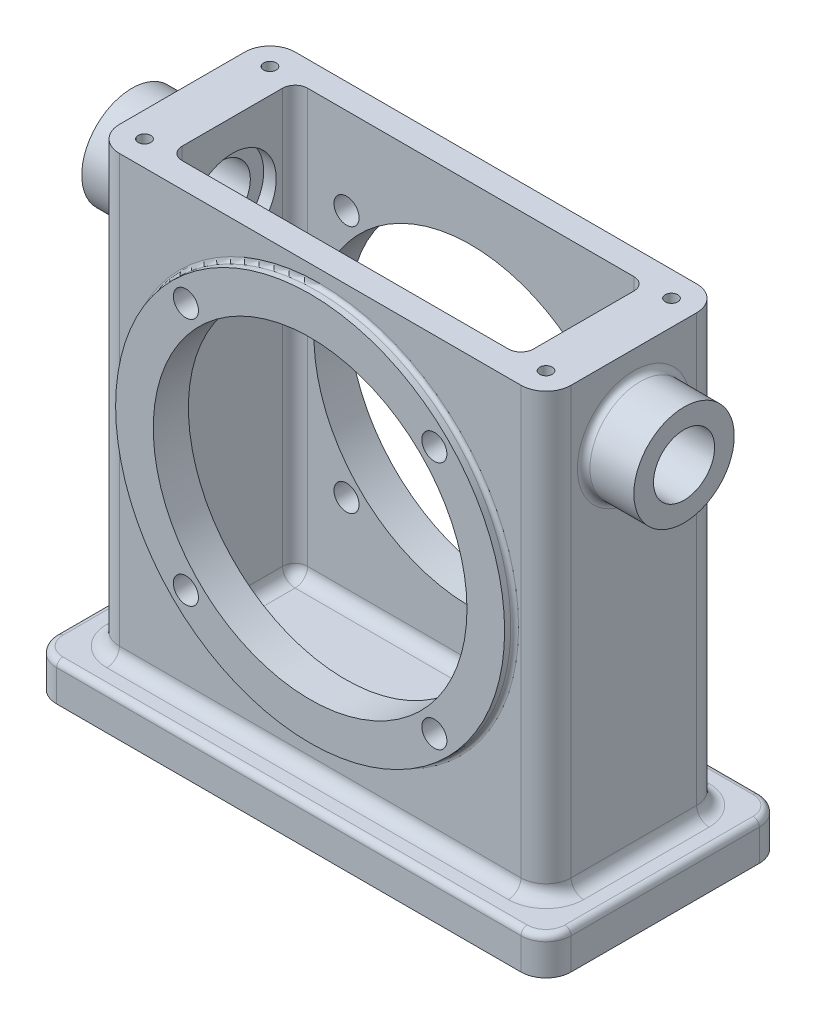
SolidWorks part; units mm, degrees
note: '?' marks a value the reader was unsure of.
ref_plane "Front" through (0, 0, 0) normal (0, 0, 1) x (1, 0, 0)
ref_plane "Top" through (0, 0, 0) normal (0, 1, 0) x (1, 0, 0)
ref_plane "Right" through (0, 0, 0) normal (1, 0, 0) x (0, 0, -1)
other "Configuration Table"
sketch "Sketch1" plane through (0, 0, 0) normal (0, 1, 0) x (1, 0, 0)
  line L0 (-65.0875, -30.1625) -> (65.0875, 30.1625) construction
  line L1 (-65.0875, -30.1625) -> (65.0875, -30.1625)
  line L2 (-65.0875, -30.1625) -> (-65.0875, 30.1625)
  line L3 (-65.0875, 30.1625) -> (65.0875, 30.1625)
  line L4 (65.0875, -30.1625) -> (65.0875, 30.1625)
  dimension "D1" = 130.175
  dimension "D2" = 60.325
extrude "Base-Extrude" add sketch "Sketch1" along normal blind 9.525
sketch "Sketch2" plane through (0, 9.525, 0) normal (0, 1, 0) x (-1, 0, 0)
  line L0 (57.15, 22.225) -> (-57.15, -22.225) construction
  line L1 (57.15, 22.225) -> (-57.15, 22.225)
  line L2 (57.15, 22.225) -> (57.15, -22.225)
  line L3 (57.15, -22.225) -> (-57.15, -22.225)
  line L4 (-57.15, 22.225) -> (-57.15, -22.225)
  dimension "D1" = 114.3
  dimension "D2" = 44.45
extrude "Boss-Extrude1" add sketch "Sketch2" along normal blind 111.125
fillet "Fillet1" radius 6.35 8 edges at (-57.15, 65.0875, -22.225) (-57.15, 65.0875, 22.225) (57.15, 65.0875, 22.225) (57.15, 65.0875, -22.225) (-65.0875, 4.7625, -30.1625) (65.0875, 4.7625, -30.1625) (65.0875, 4.7625, 30.1625) (-65.0875, 4.7625, 30.1625)
fillet "Fillet2" radius 1.5875 8 edges at (0, 9.525, 30.1625) (-65.0875, 9.525, 0) (65.0875, 9.525, 0) (0, 9.525, -30.1625) (-63.2276, 9.525, -28.3026) (63.2276, 9.525, 28.3026) (63.2276, 9.525, -28.3026) (-63.2276, 9.525, 28.3026)
fillet "Fillet3" radius 3.175 8 edges at (-57.15, 9.525, 0) (0, 9.525, -22.225) (57.15, 9.525, 0) (0, 9.525, 22.225) (-55.2901, 9.525, 20.3651) (-55.2901, 9.525, -20.3651) (55.2901, 9.525, 20.3651) (55.2901, 9.525, -20.3651)
sketch "Sketch3" plane through (0, 120.65, 0) normal (0, 1, 0) x (-1, 0, 0)
  line L2 (50.8, 15.875) -> (-50.8, 15.875)
  line L3 (41.275, 15.875) -> (-41.275, 15.875)
  line L5 (-50.8, -15.875) -> (50.8, -15.875)
  line L6 (-41.275, -15.875) -> (41.275, -15.875)
  line L8 (44.45, -15.875) -> (44.45, 15.875)
  line L9 (44.45, -12.7) -> (44.45, 12.7)
  line L11 (-44.45, 15.875) -> (-44.45, -15.875)
  line L12 (-44.45, 12.7) -> (-44.45, -12.7)
  arc A0 (-41.275, 15.875) -> (-44.45, 12.7) centre (-41.275, 12.7) ccw
  arc A1 (44.45, 12.7) -> (41.275, 15.875) centre (41.275, 12.7) ccw
  arc A2 (41.275, -15.875) -> (44.45, -12.7) centre (41.275, -12.7) ccw
  arc A3 (-44.45, -12.7) -> (-41.275, -15.875) centre (-41.275, -12.7) ccw
  dimension "D5" = 3.175
  dimension "D1" = 6.35
  dimension "D2" = 6.35
  dimension "D3" = 12.7
  dimension "D4" = 12.7
extrude "Cut-Extrude1" cut sketch "Sketch3" against normal blind 107.95
fillet "Fillet4" radius 3.175 8 edges at (43.5201, 12.7, 14.9451) (0, 12.7, 15.875) (-43.5201, 12.7, 14.9451) (-44.45, 12.7, 0) (-43.5201, 12.7, -14.9451) (0, 12.7, -15.875) (43.5201, 12.7, -14.9451) (44.45, 12.7, 0)
sketch "Sketch4" plane through (0, 0, 22.225) normal (0, 0, 1) x (1, 0, 0)
  line L0 (-50.8, 120.65) -> (50.8, 120.65) construction
  line L1 (0, -50) -> (0, 50) construction
  circle A0 centre (0, 67.31) radius 49.2125
  dimension "D1" = 98.425
  dimension "D2" = 53.34
extrude "Boss-Extrude2" add sketch "Sketch4" along normal blind 2.54
mirror "Mirror1" about plane through (0, 0, 0) normal (0, 0, 1) of "Boss-Extrude2"
sketch "Sketch5" plane through (0, 0, 24.765) normal (0, 0, 1) x (1, 0, 0)
  circle A0 centre (0, 67.31) radius 39.6875
  dimension "D1" = 79.375
extrude "Cut-Extrude2" cut sketch "Sketch5" against normal through all
fillet "Fillet5" radius 0.9906 2 edges at (-49.2125, 67.31, 22.225) (49.2125, 67.31, -22.225)
sketch "Sketch6" plane through (57.15, 0, 0) normal (1, 0, 0) x (0, 0, -1)
  line L0 (-23.8125, 0) -> (23.8125, 0) construction
  line L1 (0, 101.6) -> (0, 0) construction
  circle A0 centre (0, 101.6) radius 12.7
  dimension "D1" = 25.4
  dimension "D2" = 101.6
extrude "Boss-Extrude3" add sketch "Sketch6" along normal blind 12.7
sketch "Sketch7" plane through (44.45, 0, 0) normal (-1, 0, 0) x (0, 0, 1)
  circle A0 centre (0, 101.6) radius 7.7343
  dimension "D1" = 15.4686
extrude "Cut-Extrude3" cut sketch "Sketch7" against normal through all
sketch "Sketch8" plane through (44.45, 0, 0) normal (-1, 0, 0) x (0, 0, 1)
  circle A0 centre (0, 101.6) radius 11.1125
  dimension "D1" = 22.225
extrude "Cut-Extrude4" cut sketch "Sketch8" against normal blind 3.175
mirror "Mirror3" about plane through (0, 0, 0) normal (1, 0, 0) of "Cut-Extrude4", "Cut-Extrude3", "Boss-Extrude3"
fillet "Fillet6" radius 1.5875 2 edges at (57.15, 101.6, 12.7) (-57.15, 101.6, -12.7)
sketch "Sketch9" plane through (0, 0, 24.765) normal (0, 0, 1) x (1, 0, 0)
  line L0 (31.4309, 98.7409) -> (0, 67.31) construction
  line L1 (0, 67.31) -> (44.45, 67.31) construction
  circle A0 centre (0, 67.31) radius 44.45 construction
  circle A1 centre (31.4309, 98.7409) radius 3.175
  dimension "D1" = 88.9
  dimension "D2" = 6.35
  dimension "D3" = 45
extrude "Cut-Extrude5" cut sketch "Sketch9" against normal through all
ref_axis "CenterLargeHole" through (0, 67.31, -83.0711) along (0, 0, 1)?
pattern_circular "CirPattern1" count 4 over 360 about axis through (0, 67.31, 0) along (0, 0, 1) of "Cut-Extrude5"
sketch "Sketch10" plane through (0, 120.65, 0) normal (0, 1, 0) x (-1, 0, 0)
  line L0 (-41.275, -15.875) -> (41.275, -15.875) construction
  line L1 (41.275, 15.875) -> (-41.275, 15.875) construction
  line L2 (-57.15, 15.875) -> (-57.15, -15.875) construction
  circle A0 centre (-50.8, -15.875) radius 1.5875
  circle A1 centre (-50.8, 15.875) radius 1.5875
  dimension "D1" = 3.175
  dimension "D2" = 6.35
extrude "Cut-Extrude6" cut sketch "Sketch10" against normal blind 19.05
mirror "Mirror4" about plane through (0, 0, 0) normal (1, 0, 0) of "Cut-Extrude6"
sketch "Sketch11" plane through (0, 120.65, 0) normal (0, 1, 0) x (-1, 0, 0)
  line L0 (-69.85, 12.7) -> (-69.85, -12.7) construction
  line L1 (0, 0) -> (-69.85, 0)
  line L2 (0, 0) -> (0, 30.1625)
  line L3 (0, 30.1625) -> (-69.85, 30.1625)
  line L4 (-69.85, 0) -> (-69.85, 30.1625)
  line L5 (-58.7375, 30.1625) -> (58.7375, 30.1625) construction
extrude "section cut" [suppressed] cut sketch "Sketch11" against normal through all
